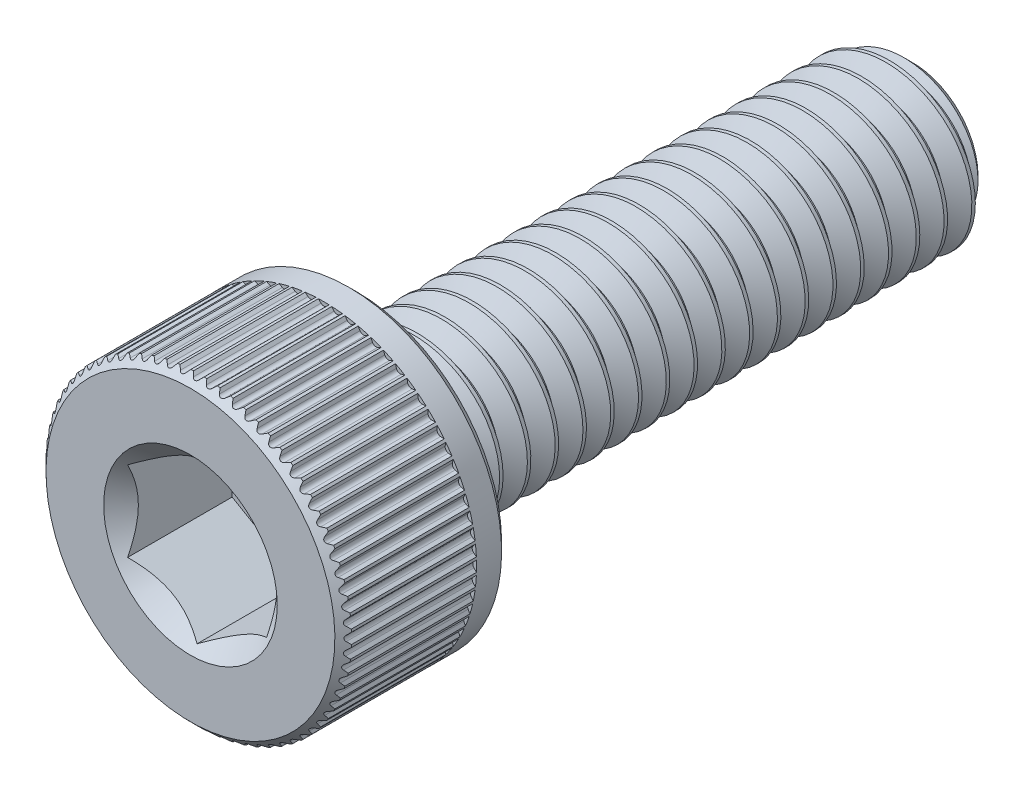
SolidWorks part; units mm, degrees
ref_plane "Front Plane" through (0, 0, 0) normal (0, 0, 1) x (1, 0, 0)
ref_plane "Top Plane" through (0, 0, 0) normal (0, 1, 0) x (1, 0, 0)
ref_plane "Right Plane" through (0, 0, 0) normal (1, 0, 0) x (0, 0, -1)
sketch "Sketch1" plane through (0, 0, 0) normal (1, 0, 0) x (0, 0, -1)
  line L0 (-6.5, 0) -> (6.5, 0) construction
  line L1 (6.5, 0) -> (6.5, 1.1752) construction
  line L2 (6.5, 1.1752) -> (6.1752, 1.5) construction
  line L3 (6.1752, 1.5) -> (6.125, 1.5) construction
  line L4 (6.125, 1.5) -> (-3.5, 1.5) construction
  line L5 (-3.5, 1.5) -> (-3.5, 2.75) construction
  line L6 (-3.5, 2.75) -> (-6.5, 2.75) construction
  line L7 (-6.5, 2.75) -> (-6.5, 0) construction
  line L8 (6.5, 1.1752) -> (6.5, 1.5) construction
  line L9 (6.4688, 1.5541) -> (6.7188, 1.1211) construction
  line L10 (6.7188, 1.1211) -> (6.9688, 1.5541) construction
  line L11 (6.9688, 1.5541) -> (6.4688, 1.5541) construction
  line L12 (6.7188, 1.5541) -> (6.7188, 1.5) construction
  line L13 (6.7188, 1.1211) -> (6.7188, 1.1752) construction
  line L14 (6.6875, 1.1752) -> (6.75, 1.1752) construction
  line L15 (6.5, 1.5) -> (6.9375, 1.5) construction
  line L16 (6.4844, 1.5271) -> (6.9531, 1.5271) construction
  line L17 (6.5, 0) -> (6.5, -1.5) construction
  line L18 (-3.65, 2.75) -> (-3.5, 2.6) construction
  line L19 (-6.35, 2.75) -> (-6.5, 2.6) construction
  line L20 (-3.5, 1.5) -> (-3.5, 0) construction
  line L21 (-3.5, 0.75) -> (-0.1667, 0.75) construction
  line L22 (-0.1667, 0.75) -> (3.1667, 0.75) construction
  line L23 (3.1667, 0.75) -> (6.5, 0.75) construction
  line L24 (-0.1667, 0.75) -> (-0.1667, 1.5) construction
  line L25 (-0.1667, 1.5) -> (-0.1667, 2.75) construction
  line L26 (3.1667, 0.75) -> (3.1667, 2.75) construction
  point P0 (-6.5, 1.25)
  point P3 (5.25, 1.5)
  point P4 (0, 0)
  point P18 (3.1667, 1.5)
  point P22 (6.7188, 1.1752)
  point P24 (6.125, 1.5)
  point P25 (6.7188, 1.5)
  point P28 (6.7188, 1.5271)
  point P29 (5.25, -1.5)
  point P30 (-0.1667, 1.5)
  point P31 (-5, 2.75)
  point P37 (-4.025, 2.75)
  point P38 (-6.275, 2.75)
  point P45 (-0.1667, 0.75)
  point P46 (3.1667, 0.75)
  dimension "D2" = 0.0625
  dimension "D7" = 0.15
  dimension "D8" = 0.15
  dimension "D9" = 0.15
  dimension "D10" = 0.075
  dimension "D11" = 0.375
  dimension "Drive Size" = 2.5
  dimension "Head Diameter" = 5.5
  dimension "Head Height" = 3
  dimension "Thread Pitch" = 0.5
  dimension "Thread Size" = 3
  dimension "Length" = 10
  dimension "D12" = 0.375
  dimension "D4" = 1.25
  dimension "D3" = 45
sketch "Sketch2" plane through (0, 0, 0) normal (1, 0, 0) x (0, 0, -1)
  line L0 (-6.5, 0) -> (-6.5, 2.6)
  line L1 (-6.35, 2.75) -> (-3.65, 2.75)
  line L2 (-3.5, 2.6) -> (-3.5, 1.65)
  line L4 (6.1752, 1.5) -> (6.5, 1.1752)
  line L5 (6.5, 1.1752) -> (6.5, 0)
  line L6 (-3.5, 2.75) -> (-6.5, 2.75) construction
  line L7 (6.5, 0) -> (-6.5, 0)
  line L8 (-6.35, 2.75) -> (-6.5, 2.6) construction
  line L10 (-6.35, 2.75) -> (-6.5, 2.6)
  line L14 (-3.65, 2.75) -> (-3.5, 2.6) construction
  line L16 (-3.65, 2.75) -> (-3.5, 2.6)
  line L17 (-3.5, 1.5) -> (-3.5, 2.75) construction
  line L19 (-3.35, 1.5) -> (6.1752, 1.5)
  line L20 (6.125, 1.5) -> (-3.5, 1.5) construction
  arc A1 (-3.5, 1.65) -> (-3.35, 1.5) centre (-3.35, 1.65) ccw
revolve "Revolve1" add sketch "Sketch2" angle 360 about L7
sketch "Sketch3" plane through (0, 0, 6.5) normal (0, 0, 1) x (1, 0, 0)
  line L1 (1.25, -0.7217) -> (1.25, 0.7217)
  line L2 (1.25, 0.7217) -> (0, 1.4434)
  line L3 (0, 1.4434) -> (-1.25, 0.7217)
  line L4 (-1.25, 0.7217) -> (-1.25, -0.7217)
  line L5 (-1.25, -0.7217) -> (0, -1.4434)
  line L6 (0, -1.4434) -> (1.25, -0.7217)
  circle A0 centre (0, 0) radius 1.25 construction
  circle A1 centre (0, 0) radius 2.75 construction
  circle A2 centre (0, 0) radius 2.75 construction
  circle A3 centre (0, 0) radius 1.4434 construction
  point P13 (0, 0)
extrude "Cut-Extrude1" cut sketch "Sketch3" against normal offset from surface (2 mm away) 1 up to face at (0, 2.6, 3.5)
sketch "Sketch4" plane through (0, 0, 6.5) normal (0, 0, 1) x (1, 0, 0)
  circle A0 centre (0, 0) radius 1.5625
  dimension "D1" = 3.125
extrude "Cut-Extrude2" cut sketch "Sketch4" against normal up to vertex (1.5 mm away) draft 45 up to point (0, 2.75, 5)
sketch "Sketch11" plane through (0, 0, 0) normal (1, 0, 0) x (0, 0, -1)
  line L0 (-6.5, 0) -> (6.5, 0) construction
  line L1 (-6.5, 0) -> (6.5, 0) construction
  line L2 (-1.625, 0) -> (-1.625, 1.5) construction
  line L3 (6.125, 1.5) -> (-3.5, 1.5) construction
  line L4 (4.625, 0) -> (4.625, 1.5) construction
  line L6 (6.5, 1.1752) -> (6.5, 1.5) construction
  point P2 (-1.625, 0)
  point P3 (4.625, 0)
  dimension "D1" = 1.875
  dimension "D2" = 1.875
sketch "Sketch6" plane through (0, 0, -6.5) normal (0, 0, -1) x (-1, 0, 0)
  circle A0 centre (0, 0) radius 1.5
curve "Helix/Spiral1" pitch 0.5 height 10.5 radius 1.5 centre (0, 0, -6.5) axis (0, 0, 1) start towards (0, 1, 0)
sketch "Sketch10" plane through (0, 0, 0) normal (1, 0, 0) x (0, 0, -1)
  line L0 (-3.35, -2.75) -> (-3.35, 2.75)
  line L5 (-6.5, 0) -> (6.5, 0) construction
  line L6 (-3.35, 1.5) -> (-3.35, -1.5) construction
  point P3 (-3.35, 0)
split "Split1" trim tools "Sketch10" bodies to split 106 resulting bodies 114 115
sketch "Sketch7" plane through (0, 0, 0) normal (1, 0, 0) x (0, 0, -1)
  line L0 (6.4844, 1.5271) -> (6.9531, 1.5271)
  line L1 (6.9531, 1.5271) -> (6.75, 1.1752)
  line L2 (6.75, 1.1752) -> (6.6875, 1.1752)
  line L3 (6.6875, 1.1752) -> (6.4844, 1.5271)
sweep "Cut-Sweep1" cut profiles "Sketch7" path "Helix/Spiral1" align with end faces yes
sketch "Sketch8" plane through (0, 0, 0) normal (1, 0, 0) x (0, 0, -1)
  line L0 (-3.5, 0) -> (-3.5, 1.5)
  line L1 (-3.35, -1.5) -> (-3.35, 1.5) construction
  line L2 (-3.5, 1.5) -> (-3.35, 1.5)
  line L4 (-3.35, 1.5) -> (-2.484, 0)
  line L5 (-2.484, 0) -> (-3.5, 0)
  line L6 (6.125, 1.5) -> (-3.5, 1.5) construction
  line L7 (-6.5, 0) -> (6.5, 0) construction
  dimension "D1" = 60
revolve "Revolve2" add sketch "Sketch8" angle 360 about L5
ref_plane "Plane1" through (0, 0, 6.5) normal (0, 0, 1) x (1, 0, 0)
sketch "Sketch12" plane through (0, 0, 6.5) normal (0, 0, 1) x (1, 0, 0)
  line L0 (0, 0) -> (0.096, 2.7483) construction
  line L1 (0, 0) -> (-0.096, 2.7483) construction
  line L2 (0, 2.6812) -> (0, 2.8187) construction
  line L3 (-0.1664, 2.8187) -> (0.1664, 2.8187)
  line L4 (-0.1664, 2.8187) -> (-0.0493, 2.7017)
  line L5 (0.0493, 2.7017) -> (0.1664, 2.8187)
  circle A0 centre (0, 0) radius 2.75 construction
  arc A1 (-0.0493, 2.7017) -> (0.0493, 2.7017) centre (0, 2.751) ccw
  point P9 (0, 2.8187)
  point P13 (0, 2.75)
  dimension "D1" = 4
  dimension "D2" = 0.0688
extrude "Cut-Extrude3" cut sketch "Sketch12" against normal blind 2.4
pattern_circular "CirPattern1" count 72 over 360 about axis through (0, 0, 6.5) along (0, 0, -1) of "Cut-Extrude3"
equation "\"D2@Sketch1\" = \"Thread Pitch@Sketch1\" / 8"
equation "\"D4@Helix/Spiral1\" = \"Thread Pitch@Sketch1\""
equation "\"D7@Sketch1\" = \"Head Height@Sketch1\" * .05"
equation "\"D8@Sketch1\"=\"D7@Sketch1\""
equation "\"D9@Sketch1\"=\"D7@Sketch1\""
equation "\"D10@Sketch1\"=\"D7@Sketch1\"/2"
equation "\"D11@Sketch1\"=\"D10@Sketch1\"*5"
equation "\"D4@Sketch1\"=\"Thread Pitch@Sketch1\"*2.5"
equation "\"D12@Sketch1\"=\"Thread Pitch@Sketch1\"*.75"
equation "\"D3@Helix/Spiral1\"=\"Length@Sketch1\"+\"Thread Pitch@Sketch1\""
equation "\"D3@Sketch2\" = \"Thread Size@Sketch1\" * 0.05"
equation "\"D1@Sketch11\"=\"Length@Sketch1\"*0.1875"
equation "\"D2@Sketch11\"=\"D1@Sketch11\""
equation "\"D2@Sketch12\"=\"Head Diameter@Sketch1\"*.0125"
equation "\"D1@Cut-Extrude3\"=\"Head Height@Sketch1\"*.8"
equation "\"D1@CirPattern1\"=\"D3@CirPattern1\"/(1.25*\"D1@Sketch12\")"
equation "\"D1@Sketch4\"=\"Drive Size@Sketch1\"*1.25"
